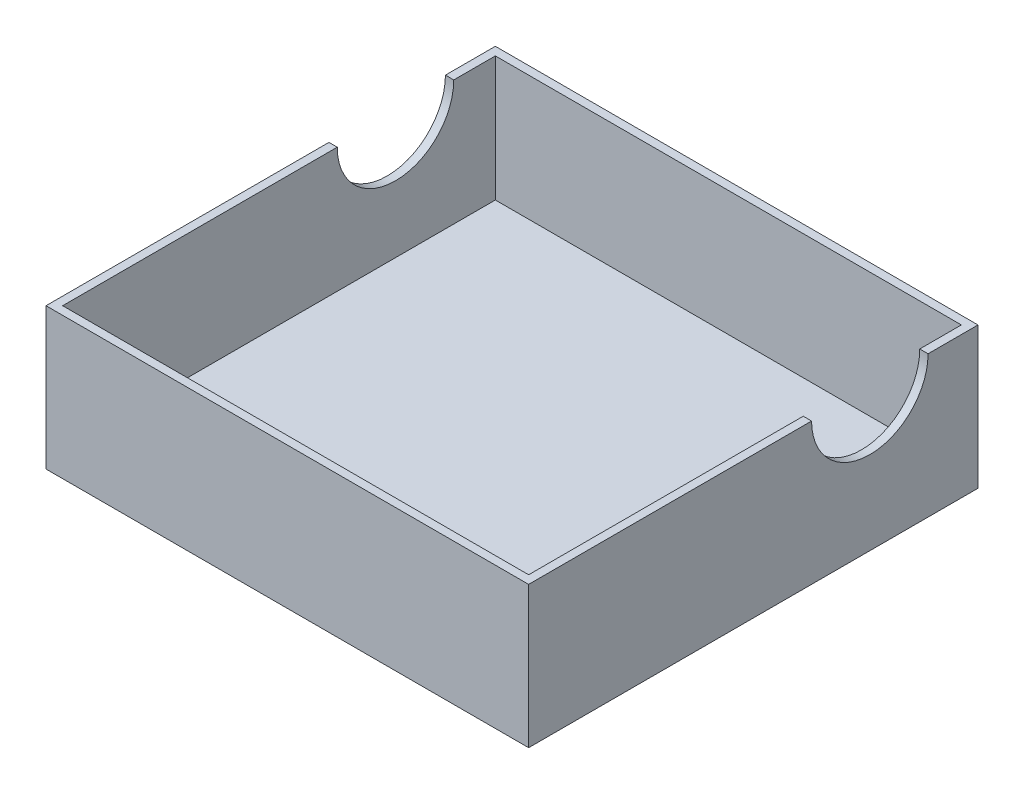
SolidWorks part; units mm, degrees
ref_plane "Plan de face" through (0, 0, 0) normal (0, 0, 1) x (1, 0, 0)
ref_plane "Plan de dessus" through (0, 0, 0) normal (0, 1, 0) x (1, 0, 0)
ref_plane "Plan de droite" through (0, 0, 0) normal (1, 0, 0) x (0, 0, -1)
sketch "Esquisse1" plane through (0, 0, 0) normal (0, 1, 0) x (1, 0, 0)
  line L0 (-22.3256, 12.3791) -> (-22.3256, -13.6209)
  line L1 (-22.3256, -13.6209) -> (5.6744, -13.6209)
  line L2 (5.6744, -13.6209) -> (5.6744, 12.3791)
  line L3 (5.6744, 12.3791) -> (-22.3256, 12.3791)
  line L4 (-22.8256, 12.8791) -> (6.1744, 12.8791)
  line L5 (6.1744, 12.8791) -> (6.1744, -14.1209)
  line L6 (6.1744, -14.1209) -> (-22.8256, -14.1209)
  line L7 (-22.8256, -14.1209) -> (-22.8256, 12.8791)
  line L8 (-22.3256, 4.8791) -> (-22.3256, 8.3791)
  line L9 (-22.3256, 8.3791) -> (-22.8256, 8.3791)
  line L10 (-22.3256, 8.3791) -> (-22.3256, 1.3791)
  line L11 (-22.3256, 1.3791) -> (-22.8256, 1.3791)
  line L12 (5.6744, -0.6209) -> (6.1744, -0.6209)
  line L13 (5.6744, 6.3791) -> (6.1744, 6.3791)
  point P3 (5.6744, 4.8791)
  point P8 (-22.3256, 4.8791)
  dimension "D1" = 26
  dimension "D2" = 28
  dimension "D3" = 0.5
  dimension "D4" = 0.5
  dimension "D5" = 0.5
  dimension "D6" = 0.5
  dimension "D7" = 7.5
  dimension "D8" = 7.5
  dimension "D9" = 3.5
  dimension "D10" = 3.5
extrude "Boss.-Extru.1" add sketch "Esquisse1" against normal blind 1 contours L2 L3 L0 L1 | L7 L6 L5 L4 L3 L2 L1 L0 | L11 L0 L9 L7 | L2 L13 L5 L4 L7 L9 L0 L3 | L13 L2 L12 L5 region at (-8.3256, 0, 0.6209) region at (-22.6228, 0, -10.3791) region at (-22.5756, 0, -4.8791) region at (5.9244, 0, -2.8791) region at (-22.6544, 0, 6.1209)
extrude "Boss.-Extru.2" add sketch "Esquisse1<3>" along normal blind 7.5 contours L7 L6 L5 L4 L3 L2 L1 L0 | L2 L13 L5 L4 L7 L9 L0 L3 region at (-22.6228, 0, -10.3791) region at (-22.6544, 0, 6.1209)
sketch "Esquisse1<3>" plane through (0, 0, 0) normal (0, 1, 0) x (1, 0, 0) same geometry as "Esquisse1"
extrude "Boss.-Extru.3" add sketch "Esquisse1<4>" along normal blind 7.5 contours L11 L0 L9 L7 | L13 L2 L12 L5 region at (-22.5756, 0, -4.8791) region at (5.9244, 0, -2.8791)
sketch "Esquisse1<4>" plane through (0, 0, 0) normal (0, 1, 0) x (1, 0, 0) same geometry as "Esquisse1"
sketch "Esquisse6" plane through (-22.8256, 0, 0) normal (-1, 0, 0) x (0, 0, 1)
  line L0 (-12.8791, -1) -> (-12.8791, 7.5) construction
  line L1 (-6.3791, 0) -> (-6.3791, 7.5)
  circle A0 centre (-6.3791, 7.5) radius 3.5
  point P0 (-12.8791, 0)
  point P1 (-8.8791, 0)
  point P4 (-6.3791, 0)
  dimension "D4" = 7
  dimension "D1" = 4
  dimension "D2" = 2.5
  dimension "D3" = 7.5
sketch "Esquisse7" plane through (6.1744, 0, 0) normal (1, 0, 0) x (0, 0, -1)
  circle A0 centre (6.3791, 7.5) radius 3.5
extrude "Enlèv. mat.-Extru.1" cut sketch "Esquisse7" against normal blind 0.5
extrude "Enlèv. mat.-Extru.2" cut sketch "Esquisse6" against normal blind 0.5 contours A0
